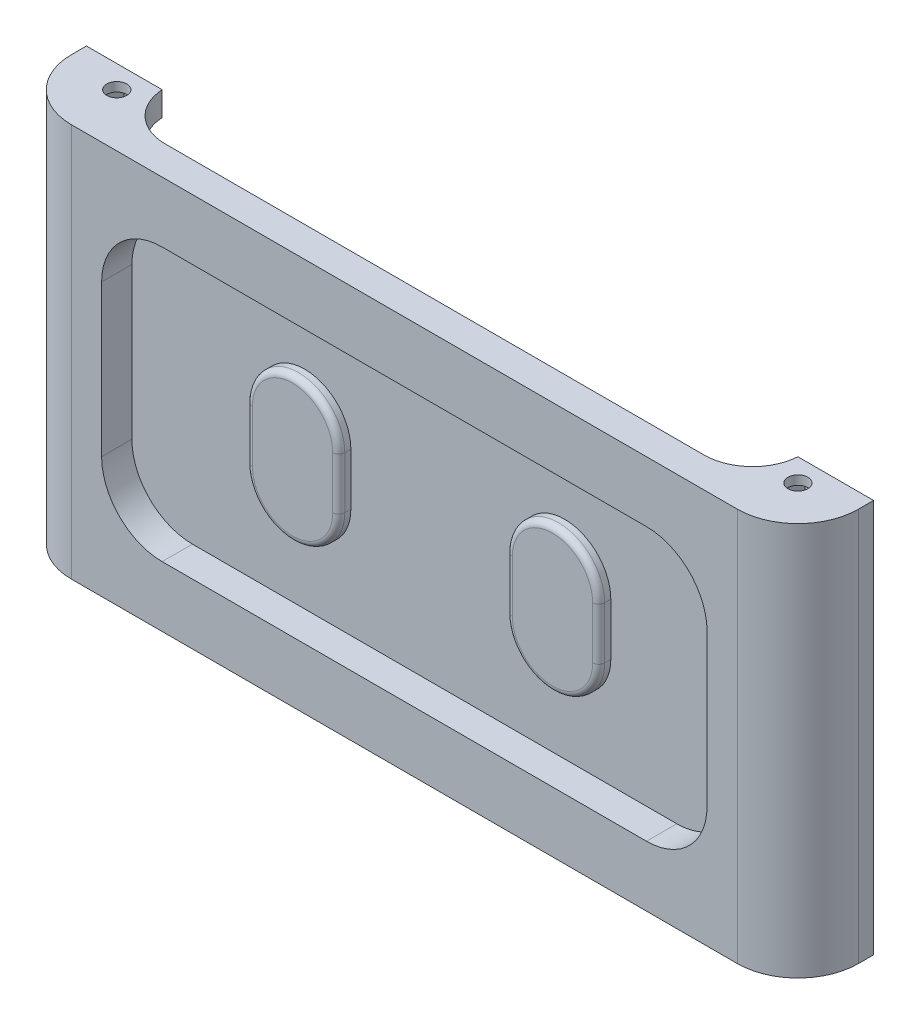
SolidWorks part; units mm, degrees
ref_plane "Front Plane" through (0, 0, 0) normal (0, 0, 1) x (1, 0, 0)
ref_plane "Top Plane" through (0, 0, 0) normal (0, 1, 0) x (1, 0, 0)
ref_plane "Right Plane" through (0, 0, 0) normal (1, 0, 0) x (0, 0, -1)
sketch "Sketch1" plane through (0, 0, 0) normal (0, 0, 1) x (1, 0, 0)
  line L1 (0, 0) -> (130, 0)
  line L2 (0, 0) -> (0, 65)
  line L3 (0, 65) -> (130, 65)
  line L4 (130, 0) -> (130, 65)
  dimension "D1" = 130
  dimension "D2" = 65
extrude "Boss-Extrude1" add sketch "Sketch1" along normal blind 12.5
sketch "Sketch4" plane through (0, 65, 0) normal (0, 1, 0) x (1, 0, 0)
  line L6 (5, 0) -> (125, 0)
  line L9 (125, 0) -> (125, -7.5)
  line L10 (5, -7.5) -> (5, 0)
  line L11 (125, -7.5) -> (5, -7.5)
  line L12 (125, 0) -> (125, -7.5)
  line L13 (5, -7.5) -> (5, 0)
  line L14 (125, -7.5) -> (5, -7.5)
  dimension "D1" = 5
extrude "Cut-Extrude3" cut sketch "Sketch4" against normal through all
sketch "Sketch2" plane through (0, 0, 12.5) normal (0, 0, 1) x (1, 0, 0)
  line L0 (65, 65) -> (65, 0) construction
  line L1 (130, 65) -> (0, 65) construction
  line L2 (0, 0) -> (130, 0) construction
  line L3 (130, 0) -> (130, 65) construction
  line L4 (15, 55) -> (115, 55)
  line L5 (15, 55) -> (15, 10)
  line L6 (15, 10) -> (115, 10)
  line L7 (115, 55) -> (115, 10)
  line L8 (15, 55) -> (115, 10) construction
  line L9 (15, 10) -> (115, 55) construction
  point P6 (65, 32.5)
  dimension "D1" = 15
  dimension "D2" = 10
extrude "Cut-Extrude1" cut sketch "Sketch2" against normal through all
fillet "Fillet1" radius 10 4 edges at (15, 10, 10) (15, 55, 10) (115, 10, 10) (115, 55, 10)
fillet "Fillet2" radius 10 2 edges at (130, 32.5, 12.5) (0, 32.5, 12.5)
sketch "Sketch5" plane through (0, 0, 0) normal (0, -1, 0) x (1, 0, 0)
  line L0 (0, 0) -> (5, 0) construction
  line L1 (5, 7.5) -> (12.5, 7.5)
  line L2 (5, 7.5) -> (5, 0)
  line L3 (5, 0) -> (12.5, 0)
  line L4 (12.5, 7.5) -> (12.5, 0)
  line L5 (125, 7.5) -> (117.5, 7.5)
  line L6 (125, 7.5) -> (125, 0)
  line L7 (125, 0) -> (117.5, 0)
  line L8 (117.5, 7.5) -> (117.5, 0)
extrude "Boss-Extrude2" add sketch "Sketch5" against normal blind 4
sketch "Sketch6" plane through (0, 4, 0) normal (0, 1, 0) x (1, 0, 0)
  line L0 (8.75, 0) -> (8.75, -7.5) construction
  line L1 (11.9254, -3.75) -> (10.3377, -1)
  line L2 (10.3377, -1) -> (7.1623, -1)
  line L3 (7.1623, -1) -> (5.5746, -3.75)
  line L4 (5.5746, -3.75) -> (7.1623, -6.5)
  line L5 (7.1623, -6.5) -> (10.3377, -6.5)
  line L6 (10.3377, -6.5) -> (11.9254, -3.75)
  line L7 (5, 0) -> (12.5, 0) construction
  line L8 (12.5, -7.5) -> (5, -7.5) construction
  line L9 (65, -12.5) -> (65, 1.5241) construction
  line L10 (120, -12.5) -> (10, -12.5) construction
  line L11 (124.4254, -3.75) -> (122.8377, -6.5)
  line L12 (122.8377, -6.5) -> (119.6623, -6.5)
  line L13 (119.6623, -6.5) -> (118.0746, -3.75)
  line L14 (118.0746, -3.75) -> (119.6623, -1)
  line L15 (119.6623, -1) -> (122.8377, -1)
  line L16 (122.8377, -1) -> (124.4254, -3.75)
  circle A0 centre (8.75, -3.75) radius 2.75 construction
  circle A1 centre (8.75, -3.75) radius 1.65
  circle A2 centre (121.25, -3.75) radius 1.65
  dimension "D1" = 3.3
  dimension "D2" = 5.5
extrude "Cut-Extrude5" cut sketch "Sketch6<2>" against normal through all contours A1 | A2 region at (8.75, 4, 3.75) region at (121.25, 4, 3.75)
sketch "Sketch6<2>" plane through (0, 4, 0) normal (0, 1, 0) x (1, 0, 0) same geometry as "Sketch6"
extrude "Cut-Extrude4" cut sketch "Sketch6" against normal blind 2.5
fillet "Fillet3" radius 8 2 edges at (117.5, 2, 7.5) (12.5, 2, 7.5)
ref_plane "Plane1" through (0, 32.5, 0) normal (0, 1, 0) x (1, 0, 0)
mirror "Mirror1" about plane through (0, 32.5, 0) normal (0, 1, 0) of "Cut-Extrude5", "Cut-Extrude4", "Boss-Extrude2", "Fillet3"
sketch "Sketch7" plane through (0, 0, 7.5) normal (0, 0, -1) x (-1, 0, 0)
  line L1 (-125, 61) -> (-5, 61)
  line L2 (-125, 61) -> (-125, 4)
  line L3 (-125, 4) -> (-5, 4)
  line L4 (-5, 61) -> (-5, 4)
extrude "Boss-Extrude3" add sketch "Sketch7" along normal blind 1 separate body
sketch "Sketch8" plane through (0, 0, 7.5) normal (0, 0, 1) x (1, 0, 0)
  line L0 (65, 55) -> (65, 24.7719) construction
  line L1 (105, 55) -> (25, 55) construction
  line L2 (25, 10) -> (105, 10) construction
  line L3 (43.5327, 36.6686) -> (86.4673, 36.6686) construction
  line L5 (65, 19.7719) -> (65, 10) construction
  line L6 (43.5327, 28.0667) -> (86.4673, 28.0667) construction
  line L7 (35.901, 36.6686) -> (35.901, 28.0667)
  line L8 (51.1643, 36.6686) -> (51.1643, 28.0667)
  line L9 (78.8357, 36.6686) -> (78.8357, 28.0667)
  line L10 (94.099, 36.6686) -> (94.099, 28.0667)
  arc A0 (51.1643, 36.6686) -> (35.901, 36.6686) centre (43.5327, 36.6686) ccw
  arc A1 (94.099, 36.6686) -> (78.8357, 36.6686) centre (86.4673, 36.6686) ccw
  arc A2 (35.901, 28.0667) -> (51.1643, 28.0667) centre (43.5327, 28.0667) ccw
  arc A3 (78.8357, 28.0667) -> (94.099, 28.0667) centre (86.4673, 28.0667) ccw
  point P11 (65, 36.6686)
extrude "Boss-Extrude4" add sketch "Sketch8" along normal blind 2 separate body contours A0 | A1 region at (43.5327, 32.3677, 7.5) region at (86.4673, 32.3677, 7.5)
sketch "Sketch9" plane through (0, 0, 6.5) normal (0, 0, -1) x (-1, 0, 0)
  line L0 (-12.5, 0) -> (-12.5, 42.5) construction
  line L1 (-20.4844, 0) -> (-109.5156, 0) construction
  line L2 (0, 0) -> (-12.5, 0) construction
  line L3 (-65, 65) -> (-65, 0) construction
  line L4 (-20.4844, 65) -> (-109.5156, 65) construction
  circle A0 centre (-12.5, 42.5) radius 4.9
  circle A1 centre (-117.5, 42.5) radius 4.9
  dimension "D3" = 9.8
  dimension "D1" = 12.5
  dimension "D2" = 42.5
extrude "Boss-Extrude6" add sketch "Sketch9" along normal blind 10 separate body
combine bodies "Combine1" operation type add bodies to combine 116 110 117
chamfer "Chamfer1" distance 2 angle 45 2 edges at (7.6, 42.5, 6.5) (112.6, 42.5, 6.5)
fillet "Fillet5" radius 1 2 edges at (7.6, 42.5, -3.5) (122.4, 42.5, -3.5)
fillet "Fillet6" radius 1 4 edges at (86.4673, 44.3003, 9.5) (94.099, 32.3677, 9.5) (86.4673, 20.4351, 9.5) (78.8357, 32.3677, 9.5)
fillet "Fillet7" radius 1 4 edges at (43.5327, 44.3003, 9.5) (51.1643, 32.3677, 9.5) (43.5327, 20.4351, 9.5) (35.901, 32.3677, 9.5)
